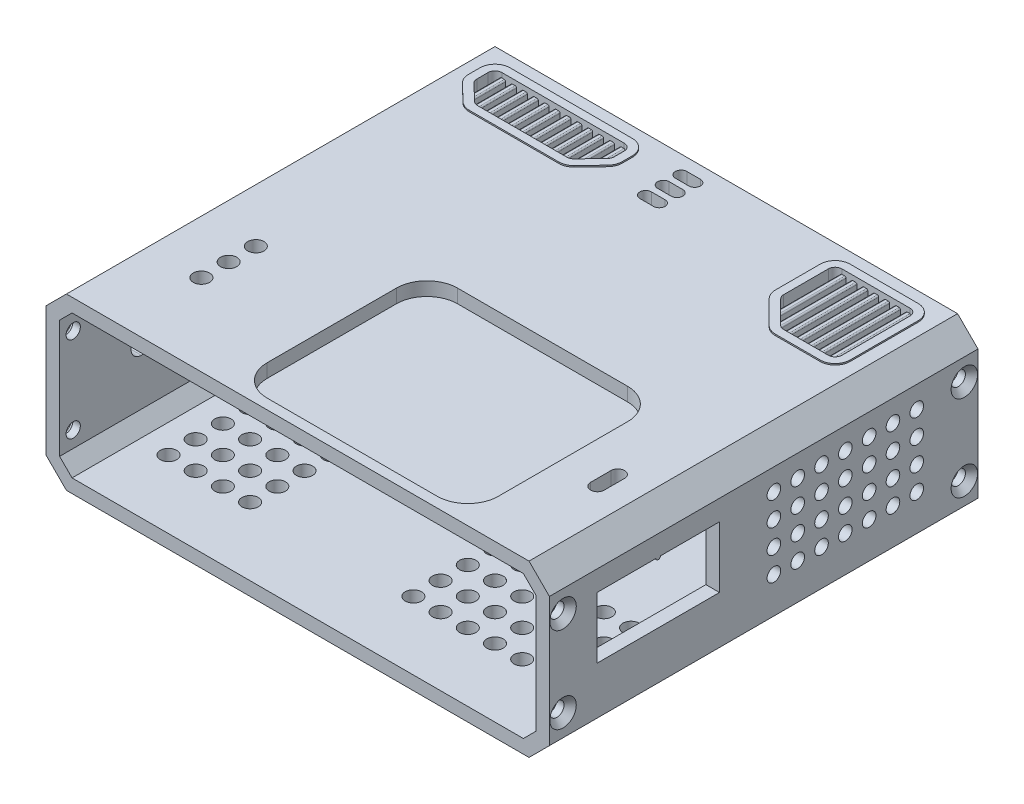
SolidWorks part; units mm, degrees
ref_plane "前视基准面" through (0, 0, 0) normal (0, 0, 1) x (1, 0, 0)
ref_plane "上视基准面" through (0, 0, 0) normal (0, 1, 0) x (1, 0, 0)
ref_plane "右视基准面" through (0, 0, 0) normal (1, 0, 0) x (0, 0, -1)
other "Configuration Table"
sketch "草图1" plane through (0, 0, 0) normal (0, 1, 0) x (1, 0, 0)
  line L1 (-36.9634, 47.435) -> (37.0366, 47.435)
  line L2 (-36.9634, 47.435) -> (-36.9634, -15.565)
  line L3 (-36.9634, -15.565) -> (37.0366, -15.565)
  line L4 (37.0366, 47.435) -> (37.0366, -15.565)
  dimension "D1" = 63
  dimension "D2" = 74
extrude "凸台-拉伸1" add sketch "草图1" along normal blind 25
chamfer "倒角1" distance 3 angle 45 4 edges at (37.0366, 0, -15.935) (-36.9634, 0, -15.935) (-36.9634, 25, -15.935) (37.0366, 25, -15.935)
sketch "草图2" plane through (0, 0, 15.565) normal (0, 0, 1) x (1, 0, 0)
  line L8 (-33.135, 2) -> (33.2082, 2)
  line L9 (35.0366, 3.8284) -> (35.0366, 21.1716)
  line L10 (33.2082, 23) -> (-33.135, 23)
  line L11 (-34.9634, 21.1716) -> (-34.9634, 3.8284)
  line L12 (-33.135, 2) -> (33.2082, 2)
  line L13 (35.0366, 3.8284) -> (35.0366, 21.1716)
  line L14 (33.2082, 23) -> (-33.135, 23)
  line L15 (-34.9634, 21.1716) -> (-34.9634, 3.8284)
  line L16 (33.2082, 2) -> (35.0366, 3.8284)
  line L17 (33.2082, 2) -> (35.0366, 3.8284)
  line L18 (35.0366, 21.1716) -> (33.2082, 23)
  line L19 (35.0366, 21.1716) -> (33.2082, 23)
  line L20 (-33.135, 23) -> (-34.9634, 21.1716)
  line L21 (-33.135, 23) -> (-34.9634, 21.1716)
  line L22 (-34.9634, 3.8284) -> (-33.135, 2)
  line L23 (-34.9634, 3.8284) -> (-33.135, 2)
  dimension "D1" = 2
extrude "切除-拉伸1" cut sketch "草图2" against normal through all
sketch "草图4" plane through (0, 25, 0) normal (0, 1, 0) x (1, 0, 0)
  line L0 (34.0366, 47.435) -> (-33.9634, 47.435) construction
  line L1 (-5.9634, 13.935) -> (19.0366, 13.935)
  line L2 (-10.4634, 9.435) -> (-10.4634, -9.565)
  line L3 (-5.9634, -14.065) -> (19.0366, -14.065)
  line L4 (23.5366, 9.435) -> (23.5366, -9.565)
  line L5 (-33.9634, -15.565) -> (34.0366, -15.565) construction
  line L7 (37.0366, 47.435) -> (37.0366, -15.565) construction
  arc A0 (19.0366, -14.065) -> (23.5366, -9.565) centre (19.0366, -9.565) ccw
  arc A1 (19.0366, 13.935) -> (23.5366, 9.435) centre (19.0366, 9.435) cw
  arc A2 (-10.4634, -9.565) -> (-5.9634, -14.065) centre (-5.9634, -9.565) ccw
  arc A3 (-5.9634, 13.935) -> (-10.4634, 9.435) centre (-5.9634, 9.435) ccw
  point P14 (23.5366, -14.065)
  point P17 (23.5366, 13.935)
  point P22 (-10.4634, 13.935)
  dimension "D5" = 4.5
  dimension "D1" = 34
  dimension "D2" = 1.5
  dimension "D3" = 33.5
  dimension "D4" = 13.5
extrude "切除-拉伸2" cut sketch "草图4" against normal up to next
sketch "草图5" plane through (0, 25, 0) normal (0, 1, 0) x (1, 0, 0)
  line L0 (-36.9634, 0.435) -> (-43.9993, 0.435) construction
  circle A0 centre (-26.1174, 0.435) radius 1.2
  circle A1 centre (-26.1174, 4.435) radius 1.2
  circle A2 centre (-26.1174, -3.565) radius 1.2
  dimension "D3" = 2.4
  dimension "D1" = 4
  dimension "D2" = 4
extrude "切除-拉伸3" cut sketch "草图5" against normal up to next
sketch "草图6" plane through (37.0366, 0, 0) normal (1, 0, 0) x (0, 0, -1)
  line L0 (-15.565, 22) -> (-15.565, 3) construction
  line L1 (-15.565, 3) -> (47.435, 3) construction
  line L2 (47.435, 22) -> (47.435, 3) construction
  line L3 (47.435, 22) -> (-15.565, 22) construction
  circle A0 centre (-13.565, 18.8) radius 1.05
  circle A1 centre (-13.565, 6.2) radius 1.05
  circle A2 centre (45.435, 6.2) radius 1.05
  circle A3 centre (45.435, 18.8) radius 1.05
  dimension "D1" = 2.1
  dimension "D2" = 2
  dimension "D3" = 3.2
  dimension "D4" = 2
  dimension "D5" = 3.2
extrude "切除-拉伸4" cut sketch "草图6" against normal through all
chamfer "倒角2" distance 0.9 angle 45 8 edges at (37.0366, 18.8, -46.485) (37.0366, 6.2, -46.485) (37.0366, 18.8, 12.515) (37.0366, 6.2, 12.515) (-36.9634, 6.2, -46.485) (-36.9634, 18.8, -46.485) (-36.9634, 6.2, 12.515) (-36.9634, 18.8, 12.515)
sketch "草图7" plane through (0, 25, 0) normal (0, 1, 0) x (1, 0, 0)
  line L0 (34.0366, 0.435) -> (47.8552, 0.435) construction
  line L2 (29.5366, 1.9891) -> (29.5366, -1.0109) construction
  line L3 (30.5366, 1.9891) -> (30.5366, -1.0109)
  line L4 (28.5366, 1.9891) -> (28.5366, -1.0109)
  line L5 (37.0366, 47.435) -> (37.0366, -15.565) construction
  arc A0 (30.5366, 1.9891) -> (28.5366, 1.9891) centre (29.5366, 1.9891) ccw
  arc A1 (28.5366, -1.0109) -> (30.5366, -1.0109) centre (29.5366, -1.0109) ccw
  point P3 (29.5366, 0.4891)
  dimension "D3" = 1
  dimension "D1" = 7.5
  dimension "D2" = 3
extrude "切除-拉伸5" cut sketch "草图7" against normal up to next
sketch "草图8" plane through (-36.9634, 0, 0) normal (-1, 0, 0) x (0, 0, 1)
  line L0 (-2.435, 11.4156) -> (-2.435, -8.1835) construction
  line L1 (-8.435, 12.2) -> (3.565, 12.2) construction
  line L2 (-8.435, 13.7) -> (3.565, 13.7)
  line L3 (-8.435, 10.7) -> (3.565, 10.7)
  line L5 (-47.435, 25) -> (15.565, 25) construction
  line L6 (15.565, 22) -> (15.565, 3) construction
  arc A0 (-8.435, 13.7) -> (-8.435, 10.7) centre (-8.435, 12.2) ccw
  arc A1 (3.565, 10.7) -> (3.565, 13.7) centre (3.565, 12.2) ccw
  point P3 (-2.435, 12.2)
  dimension "D4" = 1.5
  dimension "D1" = 18
  dimension "D2" = 12
  dimension "D3" = 12.8
extrude "切除-拉伸6" cut sketch "草图8" against normal up to next
sketch "草图9" plane through (-36.9634, 0, 0) normal (-1, 0, 0) x (0, 0, 1)
  line L1 (-7.435, 7) -> (-3.435, 7)
  line L2 (-7.435, 7) -> (-7.435, 5)
  line L3 (-7.435, 5) -> (-3.435, 5)
  line L4 (-3.435, 7) -> (-3.435, 5)
  line L5 (-47.435, 25) -> (15.565, 25) construction
  line L6 (15.565, 22) -> (15.565, 3) construction
  dimension "D1" = 19
  dimension "D2" = 2
  dimension "D3" = 18
  dimension "D4" = 4
extrude "切除-拉伸7" cut sketch "草图9" against normal up to next
fillet "圆角1" radius 1 4 edges at (-35.9634, 5, -3.435) (-35.9634, 7, -3.435) (-35.9634, 7, -7.435) (-35.9634, 5, -7.435)
sketch "草图10" plane through (-36.9634, 0, 0) normal (-1, 0, 0) x (0, 0, 1)
  line L0 (-47.435, 25) -> (15.565, 25) construction
  line L3 (15.565, 22) -> (15.565, 3) construction
  circle A0 centre (6.465, 19) radius 1
  circle A1 centre (3.265, 19) radius 1
  circle A2 centre (0.065, 19) radius 1
  circle A3 centre (-3.135, 19) radius 1
  circle A4 centre (-6.335, 19) radius 1
  circle A5 centre (3.265, 15.8) radius 1
  circle A6 centre (0.065, 15.8) radius 1
  circle A7 centre (-3.135, 15.8) radius 1
  circle A8 centre (-6.335, 15.8) radius 1
  circle A9 centre (6.465, 15.8) radius 1
  circle A10 centre (-9.535, 19) radius 1
  circle A11 centre (-12.735, 19) radius 1
  circle A12 centre (-15.935, 19) radius 1
  circle A13 centre (-19.135, 19) radius 1
  circle A14 centre (-22.335, 19) radius 1
  circle A15 centre (-25.535, 19) radius 1
  circle A16 centre (-28.735, 19) radius 1
  circle A17 centre (-31.935, 19) radius 1
  circle A18 centre (-35.135, 19) radius 1
  circle A19 centre (-38.335, 19) radius 1
  circle A20 centre (-9.535, 15.8) radius 1
  circle A21 centre (-12.735, 15.8) radius 1
  circle A22 centre (-15.935, 15.8) radius 1
  circle A23 centre (-19.135, 15.8) radius 1
  circle A24 centre (-22.335, 15.8) radius 1
  circle A25 centre (-25.535, 15.8) radius 1
  circle A26 centre (-28.735, 15.8) radius 1
  circle A27 centre (-31.935, 15.8) radius 1
  circle A28 centre (-35.135, 15.8) radius 1
  circle A29 centre (-38.335, 15.8) radius 1
  dimension "D3" = 2
  dimension "D1" = 6
  dimension "D2" = 9.1
  dimension "D4" = 15
  dimension "D5" = 2
extrude "切除-拉伸8" cut sketch "草图10" against normal up to next (2 mm away)
sketch "草图11" plane through (37.0366, 0, 0) normal (1, 0, 0) x (0, 0, -1)
  line L1 (-8.565, 19) -> (9.435, 19)
  line L3 (-8.565, 10) -> (9.435, 10)
  line L5 (-15.565, 25) -> (47.435, 25) construction
  line L18 (-8.565, 19) -> (-8.565, 10)
  line L19 (9.435, 19) -> (9.435, 10)
  line L20 (-15.565, 22) -> (-15.565, 3) construction
  dimension "D1" = 18
  dimension "D2" = 7
  dimension "D3" = 6
  dimension "D4" = 9
extrude "切除-拉伸9" cut sketch "草图11" against normal up to next
sketch "草图12" plane through (0, 0, -47.435) normal (0, 0, -1) x (-1, 0, 0)
  line L0 (-33.2082, 23) -> (33.135, 23) construction
  line L1 (24.9634, 23) -> (26.9634, 23)
  line L2 (24.9634, 23) -> (24.9634, 15.7)
  line L3 (24.9634, 15.7) -> (26.9634, 15.7)
  line L4 (26.9634, 23) -> (26.9634, 15.7)
  line L5 (36.9634, 22) -> (36.9634, 3) construction
  line L6 (-17.0366, 23) -> (-15.0366, 23)
  line L7 (-17.0366, 23) -> (-17.0366, 15.7)
  line L8 (-17.0366, 15.7) -> (-15.0366, 15.7)
  line L9 (-15.0366, 23) -> (-15.0366, 15.7)
  line L10 (-37.0366, 22) -> (-37.0366, 3) construction
  dimension "D1" = 2
  dimension "D2" = 10
  dimension "D3" = 20
  dimension "D4" = 7.3
extrude "凸台-拉伸2" add sketch "草图12" against normal blind 20
chamfer "倒角3" distance 6 angle 45 2 edges at (16.0366, 15.7, -27.435) (-25.9634, 15.7, -27.435)
sketch "草图13" plane through (0, 0, -47.435) normal (0, 0, -1) x (-1, 0, 0)
  line L0 (24.9634, 15.7) -> (26.9634, 15.7) construction
  line L1 (-33.2082, 23) -> (33.135, 23)
  line L2 (-33.2082, 23) -> (-33.2082, 15.7)
  line L3 (-33.2082, 15.7) -> (33.135, 15.7)
  line L4 (33.135, 23) -> (33.135, 15.7)
extrude "切除-拉伸10" cut sketch "草图13" against normal blind 10
sketch "草图15" plane through (37.0366, 0, 0) normal (1, 0, 0) x (0, 0, -1)
  line L0 (-15.565, 25) -> (47.435, 25) construction
  line L1 (47.435, 25) -> (47.435, 22) construction
  circle A0 centre (38.435, 18.8) radius 1
  circle A1 centre (34.935, 18.8) radius 1
  circle A2 centre (31.435, 18.8) radius 1
  circle A3 centre (27.935, 18.8) radius 1
  circle A4 centre (24.435, 18.8) radius 1
  circle A5 centre (20.935, 18.8) radius 1
  circle A6 centre (17.435, 18.8) radius 1
  circle A7 centre (34.935, 15.3) radius 1
  circle A8 centre (31.435, 15.3) radius 1
  circle A9 centre (27.935, 15.3) radius 1
  circle A10 centre (24.435, 15.3) radius 1
  circle A11 centre (20.935, 15.3) radius 1
  circle A12 centre (17.435, 15.3) radius 1
  circle A13 centre (34.935, 11.8) radius 1
  circle A14 centre (31.435, 11.8) radius 1
  circle A15 centre (27.935, 11.8) radius 1
  circle A16 centre (24.435, 11.8) radius 1
  circle A17 centre (20.935, 11.8) radius 1
  circle A18 centre (17.435, 11.8) radius 1
  circle A19 centre (34.935, 8.3) radius 1
  circle A20 centre (31.435, 8.3) radius 1
  circle A21 centre (27.935, 8.3) radius 1
  circle A22 centre (24.435, 8.3) radius 1
  circle A23 centre (20.935, 8.3) radius 1
  circle A24 centre (17.435, 8.3) radius 1
  circle A25 centre (38.435, 15.3) radius 1
  circle A26 centre (38.435, 11.8) radius 1
  circle A27 centre (38.435, 8.3) radius 1
  dimension "D1" = 2
  dimension "D4" = 7
  dimension "D2" = 6.2
  dimension "D3" = 9
  dimension "D5" = 4
extrude "切除-拉伸12" cut sketch "草图15" against normal up to next (2 mm away)
sketch "草图16" plane through (0, 23, 0) normal (0, -1, 0) x (1, 0, 0)
  line L1 (-28.599, -18.535) -> (-26.599, -18.535)
  line L2 (-28.599, -18.535) -> (-28.599, -15.535)
  line L3 (-28.599, -15.535) -> (-26.599, -15.535)
  line L4 (-26.599, -18.535) -> (-26.599, -15.535)
  line L5 (33.2082, -47.435) -> (-33.135, -47.435) construction
  line L6 (26.6682, -18.535) -> (28.6682, -18.535)
  line L7 (26.6682, -18.535) -> (26.6682, -15.535)
  line L8 (26.6682, -15.535) -> (28.6682, -15.535)
  line L9 (28.6682, -18.535) -> (28.6682, -15.535)
  line L10 (-33.135, -47.435) -> (-33.135, 15.565) construction
  line L11 (33.2082, -47.435) -> (33.2082, 15.565) construction
  dimension "D1" = 31.9
  dimension "D2" = 4.5359
  dimension "D3" = 4.54
  dimension "D4" = 2
  dimension "D5" = 3
extrude "凸台-拉伸3" add sketch "草图16" along normal blind 4
sketch "草图18" plane through (0, 2, 0) normal (0, 1, 0) x (1, 0, 0)
  line L0 (33.6224, 49.435) -> (-33.5492, 49.435) construction
  line L1 (37.0366, -15.565) -> (37.0366, 47.435) construction
  line L2 (37.0366, 43.485) -> (37.0366, 47.385) construction
  circle A0 centre (27.0366, 6.435) radius 1.2
  circle A1 centre (23.0366, 6.435) radius 1.2
  circle A2 centre (19.0366, 6.435) radius 1.2
  circle A3 centre (15.0366, 6.435) radius 1.2
  circle A4 centre (11.0366, 6.435) radius 1.2
  circle A5 centre (7.0366, 6.435) radius 1.2
  circle A6 centre (23.0366, 2.435) radius 1.2
  circle A7 centre (19.0366, 2.435) radius 1.2
  circle A8 centre (15.0366, 2.435) radius 1.2
  circle A9 centre (11.0366, 2.435) radius 1.2
  circle A10 centre (7.0366, 2.435) radius 1.2
  circle A11 centre (23.0366, -1.565) radius 1.2
  circle A12 centre (19.0366, -1.565) radius 1.2
  circle A13 centre (15.0366, -1.565) radius 1.2
  circle A14 centre (11.0366, -1.565) radius 1.2
  circle A15 centre (7.0366, -1.565) radius 1.2
  circle A16 centre (23.0366, -5.565) radius 1.2
  circle A17 centre (19.0366, -5.565) radius 1.2
  circle A18 centre (15.0366, -5.565) radius 1.2
  circle A19 centre (11.0366, -5.565) radius 1.2
  circle A20 centre (7.0366, -5.565) radius 1.2
  circle A26 centre (27.0366, 2.435) radius 1.2
  circle A27 centre (27.0366, -1.565) radius 1.2
  circle A28 centre (27.0366, -5.565) radius 1.2
  circle A30 centre (-16.9634, 6.435) radius 1.2
  circle A31 centre (-20.9634, 6.435) radius 1.2
  circle A32 centre (-24.9634, 6.435) radius 1.2
  circle A33 centre (-20.9634, 2.435) radius 1.2
  circle A34 centre (-24.9634, 2.435) radius 1.2
  circle A35 centre (-20.9634, -1.565) radius 1.2
  circle A36 centre (-24.9634, -1.565) radius 1.2
  circle A37 centre (-20.9634, -5.565) radius 1.2
  circle A38 centre (-24.9634, -5.565) radius 1.2
  circle A41 centre (-16.9634, 2.435) radius 1.2
  circle A42 centre (-16.9634, -1.565) radius 1.2
  circle A43 centre (-16.9634, -5.565) radius 1.2
  circle A45 centre (-28.9634, 6.435) radius 1.2
  circle A46 centre (-28.9634, 2.435) radius 1.2
  circle A47 centre (-28.9634, -1.565) radius 1.2
  circle A48 centre (-28.9634, -5.565) radius 1.2
  dimension "D3" = 2.4
  dimension "D1" = 43
  dimension "D2" = 10
  dimension "D6" = 54
  dimension "D4" = 6
  dimension "D5" = 4
  dimension "D7" = 4
  dimension "D8" = 4
extrude "切除-拉伸13" cut sketch "草图18" against normal through all
sketch "草图19" plane through (37.0366, 0, 0) normal (1, 0, 0) x (0, 0, -1)
  line L0 (9.435, 19) -> (-8.565, 19) construction
  circle A0 centre (0.435, 19) radius 0.325
  dimension "D1" = 0.65
extrude "凸台-拉伸4" add sketch "草图19" against normal blind 2
sketch "草图21" plane through (0, 25, 0) normal (0, 1, 0) x (1, 0, 0)
  line L1 (31.0366, 43.435) -> (31.0366, 33.435)
  line L2 (30.0366, 32.435) -> (23.4508, 32.435)
  line L3 (22.7437, 32.7279) -> (19.3295, 36.1421)
  line L4 (19.0366, 36.8492) -> (19.0366, 43.435)
  line L5 (20.0366, 44.435) -> (30.0366, 44.435)
  line L6 (-11.9634, 44.435) -> (-29.9634, 44.435)
  line L7 (-30.9634, 43.435) -> (-30.9634, 41.7558)
  line L8 (-30.6564, 41.0349) -> (-28.2421, 38.7141)
  line L9 (-27.5491, 38.435) -> (-14.3776, 38.435)
  line L10 (-13.6567, 38.742) -> (-11.2425, 41.2535)
  line L11 (-10.9634, 41.9465) -> (-10.9634, 43.435)
  line L12 (34.0366, 47.435) -> (-33.9634, 47.435) construction
  line L13 (34.0366, -15.565) -> (34.0366, 47.435) construction
  line L14 (-33.9634, 47.435) -> (-33.9634, -15.565) construction
  line L26 (-11.9634, 45.635) -> (-29.9634, 45.635)
  line L27 (-32.1634, 43.435) -> (-32.1634, 41.7558)
  line L28 (-31.488, 40.1697) -> (-29.0737, 37.849)
  line L29 (-27.5491, 37.235) -> (-14.3776, 37.235)
  line L30 (-12.7916, 37.9104) -> (-10.3773, 40.4219)
  line L31 (-9.7634, 41.9465) -> (-9.7634, 43.435)
  line L32 (32.2366, 43.435) -> (32.2366, 33.435)
  line L33 (30.0366, 31.235) -> (23.4508, 31.235)
  line L34 (21.8952, 31.8794) -> (18.481, 35.2936)
  line L35 (17.8366, 36.8492) -> (17.8366, 43.435)
  line L36 (20.0366, 45.635) -> (30.0366, 45.635)
  arc A0 (31.0366, 43.435) -> (30.0366, 44.435) centre (30.0366, 43.435) ccw
  arc A1 (31.0366, 33.435) -> (30.0366, 32.435) centre (30.0366, 33.435) cw
  arc A2 (23.4508, 32.435) -> (22.7437, 32.7279) centre (23.4508, 33.435) cw
  arc A3 (19.3295, 36.1421) -> (19.0366, 36.8492) centre (20.0366, 36.8492) cw
  arc A4 (19.0366, 43.435) -> (20.0366, 44.435) centre (20.0366, 43.435) cw
  arc A5 (-14.3776, 38.435) -> (-13.6567, 38.742) centre (-14.3776, 39.435) ccw
  arc A6 (-28.2421, 38.7141) -> (-27.5491, 38.435) centre (-27.5491, 39.435) ccw
  arc A7 (-30.9634, 41.7558) -> (-30.6564, 41.0349) centre (-29.9634, 41.7558) ccw
  arc A8 (-11.2425, 41.2535) -> (-10.9634, 41.9465) centre (-11.9634, 41.9465) ccw
  arc A9 (-10.9634, 43.435) -> (-11.9634, 44.435) centre (-11.9634, 43.435) ccw
  arc A10 (-29.9634, 44.435) -> (-30.9634, 43.435) centre (-29.9634, 43.435) ccw
  arc A11 (-29.9634, 45.635) -> (-32.1634, 43.435) centre (-29.9634, 43.435) ccw
  arc A12 (-32.1634, 41.7558) -> (-31.488, 40.1697) centre (-29.9634, 41.7558) ccw
  arc A13 (-29.0737, 37.849) -> (-27.5491, 37.235) centre (-27.5491, 39.435) ccw
  arc A14 (-14.3776, 37.235) -> (-12.7916, 37.9104) centre (-14.3776, 39.435) ccw
  arc A15 (-10.3773, 40.4219) -> (-9.7634, 41.9465) centre (-11.9634, 41.9465) ccw
  arc A16 (-9.7634, 43.435) -> (-11.9634, 45.635) centre (-11.9634, 43.435) ccw
  arc A17 (32.2366, 33.435) -> (30.0366, 31.235) centre (30.0366, 33.435) cw
  arc A18 (23.4508, 31.235) -> (21.8952, 31.8794) centre (23.4508, 33.435) cw
  arc A19 (18.481, 35.2936) -> (17.8366, 36.8492) centre (20.0366, 36.8492) cw
  arc A20 (17.8366, 43.435) -> (20.0366, 45.635) centre (20.0366, 43.435) cw
  arc A21 (32.2366, 43.435) -> (30.0366, 45.635) centre (30.0366, 43.435) ccw
  point P21 (-20.9634, 38.435)
  point P22 (-20.9634, 44.435)
  point P25 (31.0366, 44.435)
  point P28 (31.0366, 32.435)
  point P31 (23.0366, 32.435)
  point P34 (19.0366, 36.435)
  point P37 (19.0366, 44.435)
  point P40 (-13.9518, 38.435)
  point P43 (-27.9518, 38.435)
  point P50 (-10.9634, 44.435)
  point P53 (-30.9634, 44.435)
  dimension "D11" = 1
  dimension "D1" = 3
  dimension "D2" = 3
  dimension "D3" = 3
  dimension "D4" = 20
  dimension "D5" = 12
  dimension "D6" = 12
  dimension "D7" = 8
  dimension "D8" = 8
  dimension "D9" = 14
  dimension "D10" = 6
  dimension "D12" = 1.2
  dimension "D13" = 1.2
extrude "凸台-拉伸5" add sketch "草图21" along normal blind 0.2
sketch "草图22" plane through (0, 25, 0) normal (0, 1, 0) x (1, 0, 0)
  line L22 (-13.6567, 38.742) -> (-11.2425, 41.2535) construction
  line L23 (-10.9634, 41.9465) -> (-10.9634, 43.435) construction
  line L24 (-11.9634, 44.435) -> (-29.9634, 44.435) construction
  line L25 (-30.9634, 43.435) -> (-30.9634, 41.7558) construction
  line L26 (-30.6564, 41.0349) -> (-28.2421, 38.7141) construction
  line L27 (-27.5491, 38.435) -> (-14.3776, 38.435) construction
  line L28 (30.0366, 44.435) -> (20.0366, 44.435) construction
  line L29 (19.0366, 43.435) -> (19.0366, 36.8492) construction
  line L30 (19.3295, 36.1421) -> (22.7437, 32.7279) construction
  line L31 (23.4508, 32.435) -> (30.0366, 32.435) construction
  line L32 (31.0366, 33.435) -> (31.0366, 43.435) construction
  line L33 (-13.6567, 38.742) -> (-11.2425, 41.2535)
  line L34 (-10.9634, 41.9465) -> (-10.9634, 43.435)
  line L35 (-11.9634, 44.435) -> (-29.9634, 44.435)
  line L36 (-30.9634, 43.435) -> (-30.9634, 41.7558)
  line L37 (-30.6564, 41.0349) -> (-28.2421, 38.7141)
  line L38 (-27.5491, 38.435) -> (-14.3776, 38.435)
  line L39 (30.0366, 44.435) -> (20.0366, 44.435)
  line L40 (19.0366, 43.435) -> (19.0366, 36.8492)
  line L41 (19.3295, 36.1421) -> (22.7437, 32.7279)
  line L42 (23.4508, 32.435) -> (30.0366, 32.435)
  line L43 (31.0366, 33.435) -> (31.0366, 43.435)
  arc A0 (-14.3776, 38.435) -> (-13.6567, 38.742) centre (-14.3776, 39.435) ccw construction
  arc A1 (-11.2425, 41.2535) -> (-10.9634, 41.9465) centre (-11.9634, 41.9465) ccw construction
  arc A2 (-10.9634, 43.435) -> (-11.9634, 44.435) centre (-11.9634, 43.435) ccw construction
  arc A3 (-29.9634, 44.435) -> (-30.9634, 43.435) centre (-29.9634, 43.435) ccw construction
  arc A4 (-30.9634, 41.7558) -> (-30.6564, 41.0349) centre (-29.9634, 41.7558) ccw construction
  arc A5 (-28.2421, 38.7141) -> (-27.5491, 38.435) centre (-27.5491, 39.435) ccw construction
  arc A6 (31.0366, 43.435) -> (30.0366, 44.435) centre (30.0366, 43.435) ccw construction
  arc A7 (20.0366, 44.435) -> (19.0366, 43.435) centre (20.0366, 43.435) ccw construction
  arc A8 (19.0366, 36.8492) -> (19.3295, 36.1421) centre (20.0366, 36.8492) ccw construction
  arc A9 (22.7437, 32.7279) -> (23.4508, 32.435) centre (23.4508, 33.435) ccw construction
  arc A10 (30.0366, 32.435) -> (31.0366, 33.435) centre (30.0366, 33.435) ccw construction
  arc A11 (-14.3776, 38.435) -> (-13.6567, 38.742) centre (-14.3776, 39.435) ccw
  arc A12 (-11.2425, 41.2535) -> (-10.9634, 41.9465) centre (-11.9634, 41.9465) ccw
  arc A13 (-10.9634, 43.435) -> (-11.9634, 44.435) centre (-11.9634, 43.435) ccw
  arc A14 (-29.9634, 44.435) -> (-30.9634, 43.435) centre (-29.9634, 43.435) ccw
  arc A15 (-30.9634, 41.7558) -> (-30.6564, 41.0349) centre (-29.9634, 41.7558) ccw
  arc A16 (-28.2421, 38.7141) -> (-27.5491, 38.435) centre (-27.5491, 39.435) ccw
  arc A17 (31.0366, 43.435) -> (30.0366, 44.435) centre (30.0366, 43.435) ccw
  arc A18 (20.0366, 44.435) -> (19.0366, 43.435) centre (20.0366, 43.435) ccw
  arc A19 (19.0366, 36.8492) -> (19.3295, 36.1421) centre (20.0366, 36.8492) ccw
  arc A20 (22.7437, 32.7279) -> (23.4508, 32.435) centre (23.4508, 33.435) ccw
  arc A21 (30.0366, 32.435) -> (31.0366, 33.435) centre (30.0366, 33.435) ccw
extrude "切除-拉伸15" cut sketch "草图22" against normal blind 2
ref_plane "plante" through (0, 24.5, 0) normal (0, 1, 0) x (1, 0, 0)
sketch "草图23" plane through (0, 24.5, 0) normal (0, 1, 0) x (1, 0, 0)
  line L0 (27.8366, 45.7265) -> (28.6366, 45.7265)
  line L1 (29.4366, 45.7265) -> (30.2366, 45.7265)
  line L2 (29.4366, 45.7265) -> (29.4366, 32.4528)
  line L3 (29.4366, 32.4528) -> (30.2366, 32.4528)
  line L4 (30.2366, 45.7265) -> (30.2366, 32.4528)
  line L5 (27.8366, 45.7265) -> (27.8366, 32.4528)
  line L6 (27.8366, 32.4528) -> (28.6366, 32.4528)
  line L7 (28.6366, 45.7265) -> (28.6366, 32.4528)
  line L8 (26.2366, 45.7265) -> (27.0366, 45.7265)
  line L9 (26.2366, 45.7265) -> (26.2366, 32.4528)
  line L10 (26.2366, 32.4528) -> (27.0366, 32.4528)
  line L11 (27.0366, 45.7265) -> (27.0366, 32.4528)
  line L12 (24.6366, 45.7265) -> (25.4366, 45.7265)
  line L13 (24.6366, 45.7265) -> (24.6366, 32.4528)
  line L14 (24.6366, 32.4528) -> (25.4366, 32.4528)
  line L15 (25.4366, 45.7265) -> (25.4366, 32.4528)
  line L16 (23.0366, 45.7265) -> (23.8366, 45.7265)
  line L17 (23.0366, 45.7265) -> (23.0366, 32.4528)
  line L18 (23.0366, 32.4528) -> (23.8366, 32.4528)
  line L19 (23.8366, 45.7265) -> (23.8366, 32.4528)
  line L20 (21.4366, 45.7265) -> (22.2366, 45.7265)
  line L21 (21.4366, 45.7265) -> (21.4366, 32.4528)
  line L22 (21.4366, 32.4528) -> (22.2366, 32.4528)
  line L23 (22.2366, 45.7265) -> (22.2366, 32.4528)
  line L24 (19.8366, 45.7265) -> (20.6366, 45.7265)
  line L25 (19.8366, 45.7265) -> (19.8366, 32.4528)
  line L26 (19.8366, 32.4528) -> (20.6366, 32.4528)
  line L27 (20.6366, 45.7265) -> (20.6366, 32.4528)
  line L32 (-14.1994, 46.4523) -> (-13.3994, 46.4523)
  line L33 (-12.5994, 46.4523) -> (-11.7994, 46.4523)
  line L34 (-12.5994, 46.4523) -> (-12.5994, 37.7287)
  line L35 (-12.5994, 37.7287) -> (-11.7994, 37.7287)
  line L36 (-11.7994, 46.4523) -> (-11.7994, 37.7287)
  line L37 (-14.1994, 46.4523) -> (-14.1994, 37.7287)
  line L38 (-14.1994, 37.7287) -> (-13.3994, 37.7287)
  line L39 (-13.3994, 46.4523) -> (-13.3994, 37.7287)
  line L40 (-15.7994, 46.4523) -> (-14.9994, 46.4523)
  line L41 (-15.7994, 46.4523) -> (-15.7994, 37.7287)
  line L42 (-15.7994, 37.7287) -> (-14.9994, 37.7287)
  line L43 (-14.9994, 46.4523) -> (-14.9994, 37.7287)
  line L44 (-17.3994, 46.4523) -> (-16.5994, 46.4523)
  line L45 (-17.3994, 46.4523) -> (-17.3994, 37.7287)
  line L46 (-17.3994, 37.7287) -> (-16.5994, 37.7287)
  line L47 (-16.5994, 46.4523) -> (-16.5994, 37.7287)
  line L48 (-18.9994, 46.4523) -> (-18.1994, 46.4523)
  line L49 (-18.9994, 46.4523) -> (-18.9994, 37.7287)
  line L50 (-18.9994, 37.7287) -> (-18.1994, 37.7287)
  line L51 (-18.1994, 46.4523) -> (-18.1994, 37.7287)
  line L52 (-20.5994, 46.4523) -> (-19.7994, 46.4523)
  line L53 (-20.5994, 46.4523) -> (-20.5994, 37.7287)
  line L54 (-20.5994, 37.7287) -> (-19.7994, 37.7287)
  line L55 (-19.7994, 46.4523) -> (-19.7994, 37.7287)
  line L56 (-22.1994, 46.4523) -> (-21.3994, 46.4523)
  line L57 (-22.1994, 46.4523) -> (-22.1994, 37.7287)
  line L58 (-22.1994, 37.7287) -> (-21.3994, 37.7287)
  line L59 (-21.3994, 46.4523) -> (-21.3994, 37.7287)
  line L60 (-23.7994, 46.4523) -> (-22.9994, 46.4523)
  line L61 (-23.7994, 46.4523) -> (-23.7994, 37.7287)
  line L62 (-23.7994, 37.7287) -> (-22.9994, 37.7287)
  line L63 (-22.9994, 46.4523) -> (-22.9994, 37.7287)
  line L64 (-25.3994, 46.4523) -> (-24.5994, 46.4523)
  line L65 (-25.3994, 46.4523) -> (-25.3994, 37.7287)
  line L66 (-25.3994, 37.7287) -> (-24.5994, 37.7287)
  line L67 (-24.5994, 46.4523) -> (-24.5994, 37.7287)
  line L68 (-26.9994, 46.4523) -> (-26.1994, 46.4523)
  line L69 (-26.9994, 46.4523) -> (-26.9994, 37.7287)
  line L70 (-26.9994, 37.7287) -> (-26.1994, 37.7287)
  line L71 (-26.1994, 46.4523) -> (-26.1994, 37.7287)
  line L72 (-28.5994, 46.4523) -> (-27.7994, 46.4523)
  line L73 (-28.5994, 46.4523) -> (-28.5994, 37.7287)
  line L74 (-28.5994, 37.7287) -> (-27.7994, 37.7287)
  line L75 (-27.7994, 46.4523) -> (-27.7994, 37.7287)
  line L88 (34.0366, -15.565) -> (34.0366, 47.435) construction
  line L89 (-30.1994, 46.4523) -> (-29.3994, 46.4523)
  line L90 (-30.1994, 46.4523) -> (-30.1994, 37.7287)
  line L91 (-30.1994, 37.7287) -> (-29.3994, 37.7287)
  line L92 (-29.3994, 46.4523) -> (-29.3994, 37.7287)
  dimension "D1" = 0.8
  dimension "D4" = 3.8
  dimension "D2" = 7
  dimension "D3" = 12
extrude "凸台-拉伸6" add sketch "草图23" against normal blind 1.5
fillet "圆角2" radius 0.2 38 edges at (-28.5994, 24.5, -41.7462) (-27.7994, 24.5, -41.4509) (-26.9994, 24.5, -41.435) (-26.1994, 24.5, -41.435) (-25.3994, 24.5, -41.435) (-24.5994, 24.5, -41.435) (-23.7994, 24.5, -41.435) (-22.9994, 24.5, -41.435) (-22.1994, 24.5, -41.435) (-21.3994, 24.5, -41.435) (-20.5994, 24.5, -41.435) (-19.7994, 24.5, -41.435) (-18.9994, 24.5, -41.435) (-18.1994, 24.5, -41.435) (-17.3994, 24.5, -41.435) (-16.5994, 24.5, -41.435) (-15.7994, 24.5, -41.435) (-14.9994, 24.5, -41.435) (-14.1994, 24.5, -41.443) (-13.3994, 24.5, -41.7224) (-12.5994, 24.5, -42.1385) (-11.7994, 24.5, -42.5478) (-30.1994, 24.5, -42.5011) (19.8366, 24.5, -40.0249) (20.6366, 24.5, -39.635) (21.4366, 24.5, -39.235) (22.2366, 24.5, -38.835) (23.0366, 24.5, -38.4799) (23.8366, 24.5, -38.4439) (24.6366, 24.5, -38.4439) (25.4366, 24.5, -38.4439) (26.2366, 24.5, -38.4439) (27.0366, 24.5, -38.4439) (27.8366, 24.5, -38.4439) (28.6366, 24.5, -38.4439) (29.4366, 24.5, -38.4439) (30.2366, 24.5, -38.435) (-29.3994, 24.5, -42.1307)
sketch "草图24" plane through (0, 25, 0) normal (0, 1, 0) x (1, 0, 0)
  line L0 (-3.9634, 44.785) -> (-1.9634, 44.785) construction
  line L1 (-3.9634, 45.635) -> (-1.9634, 45.635)
  line L2 (-3.9634, 43.935) -> (-1.9634, 43.935)
  line L3 (-11.9634, 45.635) -> (-29.9634, 45.635) construction
  line L4 (-33.9634, 47.435) -> (-33.9634, -15.565) construction
  line L5 (-3.9634, 42.185) -> (-1.9634, 42.185) construction
  line L6 (-3.9634, 43.035) -> (-1.9634, 43.035)
  line L7 (-3.9634, 41.335) -> (-1.9634, 41.335)
  line L8 (-3.9634, 39.585) -> (-1.9634, 39.585) construction
  line L9 (-3.9634, 40.435) -> (-1.9634, 40.435)
  line L10 (-3.9634, 38.735) -> (-1.9634, 38.735)
  arc A0 (-3.9634, 45.635) -> (-3.9634, 43.935) centre (-3.9634, 44.785) ccw
  arc A1 (-1.9634, 43.935) -> (-1.9634, 45.635) centre (-1.9634, 44.785) ccw
  arc A2 (-3.9634, 43.035) -> (-3.9634, 41.335) centre (-3.9634, 42.185) ccw
  arc A3 (-1.9634, 41.335) -> (-1.9634, 43.035) centre (-1.9634, 42.185) ccw
  arc A4 (-3.9634, 40.435) -> (-3.9634, 38.735) centre (-3.9634, 39.585) ccw
  arc A5 (-1.9634, 38.735) -> (-1.9634, 40.435) centre (-1.9634, 39.585) ccw
  point P2 (-2.9634, 44.785)
  point P14 (-2.9634, 42.185)
  point P21 (-2.9634, 39.585)
  dimension "D1" = 0.85
  dimension "D2" = 30
  dimension "D3" = 2
  dimension "D4" = 3
extrude "切除-拉伸16" cut sketch "草图24" against normal up to next
